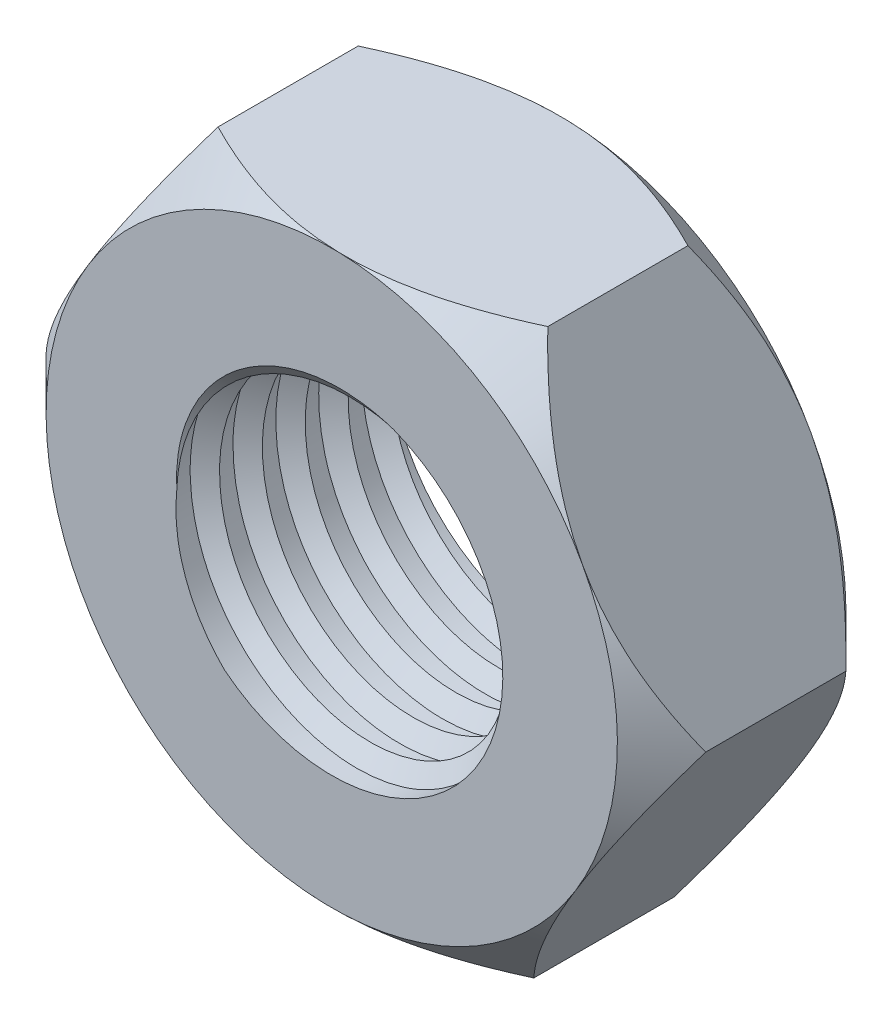
SolidWorks part; units mm, degrees
ref_plane "Front Plane" through (0, 0, 0) normal (0, 0, 1) x (1, 0, 0)
ref_plane "Top Plane" through (0, 0, 0) normal (0, 1, 0) x (1, 0, 0)
ref_plane "Right Plane" through (0, 0, 0) normal (1, 0, 0) x (0, 0, -1)
sketch "Sketch1" plane through (0, 0, 0) normal (0, 0, 1) x (1, 0, 0)
  line L1 (6.0154, 9.8564) -> (-5.5281, 10.1377)
  line L2 (-5.5281, 10.1377) -> (-11.5436, 0.2813)
  line L3 (-11.5436, 0.2813) -> (-6.0154, -9.8564)
  line L4 (-6.0154, -9.8564) -> (5.5281, -10.1377)
  line L5 (5.5281, -10.1377) -> (11.5436, -0.2813)
  line L6 (11.5436, -0.2813) -> (6.0154, 9.8564)
  circle A0 centre (0, 0) radius 10 construction
  circle A1 centre (0, 0) radius 5
  dimension "D1" = 20
  dimension "D2" = 10
extrude "Boss-Extrude1" add sketch "Sketch1" along normal blind 8
sketch "Sketch2" plane through (0, 0, 0) normal (0, 0, -1) x (-1, 0, 0)
  circle A0 centre (0, 0) radius 10
extrude "Cut-Extrude1" cut sketch "Sketch2" against normal blind 8 draft 45 flip side to cut
sketch "Sketch3" plane through (0, 0, 8) normal (0, 0, 1) x (1, 0, 0)
  circle A0 centre (0, 0) radius 10
extrude "Cut-Extrude2" cut sketch "Sketch3" against normal blind 8 draft 45 flip side to cut
sketch "Sketch4" plane through (0, 0, 8) normal (0, 0, 1) x (1, 0, 0)
  circle A0 centre (0, 0) radius 5
curve "Helix/Spiral1" pitch 1.5 height 12 radius 5 centre (0, 0, 8) axis (0, 0, -1) start towards (1, 0, 0)
sketch "Sketch5" plane through (0, 0, 0) normal (0, 1, 0) x (1, 0, 0)
  line L0 (5.9889, -7.7136) -> (5.9889, -8.5377)
  line L1 (5.9889, -7.7136) -> (4.4046, -6.4077)
  line L2 (4.4046, -6.4077) -> (3.9187, -9.3118)
  line L3 (3.9187, -9.3118) -> (5.9889, -8.5377)
  circle A0 centre (5, -8) radius 0.85 construction
  spline S0 degree 3 poles (5, -8) (5, -7.9689) (4.7397, -7.9062) (3.6276, -7.8125) (1.9632, -7.7187) (0, -7.625) (-1.9632, -7.5312) (-3.6276, -7.4375) (-4.7397, -7.3437) (-5.1302, -7.25) (-4.7397, -7.1562) (-3.6276, -7.0625) (-1.9632, -6.9687) (0, -6.875) (1.9632, -6.7812) (3.6276, -6.6875) (4.7397, -6.5937) (5.1302, -6.5) (4.7397, -6.4062) (3.6276, -6.3125) (1.9632, -6.2187) (0, -6.125) (-1.9632, -6.0312) (-3.6276, -5.9375) (-4.7397, -5.8437) (-5.1302, -5.75) (-4.7397, -5.6562) (-3.6276, -5.5625) (-1.9632, -5.4688) (0, -5.375) (1.9632, -5.2812) (3.6276, -5.1875) (4.7397, -5.0937) (5.1302, -5) (4.7397, -4.9062) (3.6276, -4.8125) (1.9632, -4.7187) (0, -4.625) (-1.9632, -4.5312) (-3.6276, -4.4375) (-4.7397, -4.3437) (-5.1302, -4.25) (-4.7397, -4.1562) (-3.6276, -4.0625) (-1.9632, -3.9687) (0, -3.875) (1.9632, -3.7812) (3.6276, -3.6875) (4.7397, -3.5937) (5.1302, -3.5) (4.7397, -3.4062) (3.6276, -3.3125) (1.9632, -3.2187) (0, -3.125) (-1.9632, -3.0312) (-3.6276, -2.9375) (-4.7397, -2.8437) (-5.1302, -2.75) (-4.7397, -2.6562) (-3.6276, -2.5625) (-1.9632, -2.4687) (0, -2.375) (1.9632, -2.2812) (3.6276, -2.1875) (4.7397, -2.0937) (5.1302, -2) (4.7397, -1.9062) (3.6276, -1.8125) (1.9632, -1.7187) (0, -1.625) (-1.9632, -1.5312) (-3.6276, -1.4375) (-4.7397, -1.3437) (-5.1302, -1.25) (-4.7397, -1.1562) (-3.6276, -1.0625) (-1.9632, -0.9687) (0, -0.875) (1.9632, -0.7812) (3.6276, -0.6875) (4.7397, -0.5937) (5.1302, -0.5) (4.7397, -0.4062) (3.6276, -0.3125) (1.9632, -0.2187) (0, -0.125) (-1.9632, -0.0312) (-3.6276, 0.0625) (-4.7397, 0.1563) (-5.1302, 0.25) (-4.7397, 0.3438) (-3.6276, 0.4375) (-1.9632, 0.5313) (0, 0.625) (1.9632, 0.7188) (3.6276, 0.8125) (4.7397, 0.9063) (5.1302, 1) (4.7397, 1.0938) (3.6276, 1.1875) (1.9632, 1.2813) (0, 1.375) (-1.9632, 1.4688) (-3.6276, 1.5625) (-4.7397, 1.6563) (-5.1302, 1.75) (-4.7397, 1.8438) (-3.6276, 1.9375) (-1.9632, 2.0313) (0, 2.125) (1.9632, 2.2188) (3.6276, 2.3125) (4.7397, 2.4062) (5.1302, 2.5) (4.7397, 2.5937) (3.6276, 2.6875) (1.9632, 2.7812) (0, 2.875) (-1.9632, 2.9687) (-3.6276, 3.0625) (-4.7397, 3.1562) (-5.1302, 3.25) (-4.7397, 3.3437) (-3.6276, 3.4375) (-1.9632, 3.5312) (0, 3.625) (1.9632, 3.7187) (3.6276, 3.8125) (4.7397, 3.9062) (5, 3.9689) (5, 4) knots 0 0 0 0 0.007813 0.015625 0.023438 0.03125 0.039063 0.046875 0.054688 0.0625 0.070313 0.078125 0.085938 0.09375 0.101563 0.109375 0.117188 0.125 0.132813 0.140625 0.148438 0.15625 0.164063 0.171875 0.179688 0.1875 0.195313 0.203125 0.210938 0.21875 0.226563 0.234375 0.242188 0.25 0.257813 0.265625 0.273438 0.28125 0.289063 0.296875 0.304688 0.3125 0.320313 0.328125 0.335938 0.34375 0.351563 0.359375 0.367188 0.375 0.382813 0.390625 0.398438 0.40625 0.414063 0.421875 0.429688 0.4375 0.445313 0.453125 0.460938 0.46875 0.476563 0.484375 0.492188 0.5 0.507813 0.515625 0.523438 0.53125 0.539063 0.546875 0.554688 0.5625 0.570313 0.578125 0.585938 0.59375 0.601563 0.609375 0.617188 0.625 0.632813 0.640625 0.648438 0.65625 0.664063 0.671875 0.679688 0.6875 0.695313 0.703125 0.710938 0.71875 0.726563 0.734375 0.742188 0.75 0.757813 0.765625 0.773438 0.78125 0.789063 0.796875 0.804688 0.8125 0.820313 0.828125 0.835938 0.84375 0.851563 0.859375 0.867188 0.875 0.882813 0.890625 0.898438 0.90625 0.914063 0.921875 0.929688 0.9375 0.945313 0.953125 0.960938 0.96875 0.976563 0.984375 0.992188 1 1 1 1 construction
  point P10 (4.1617, -7.8597)
  dimension "D1" = 1.7
sweep "Cut-Sweep1" cut profiles "Sketch5" path "Helix/Spiral1" align with end faces yes
